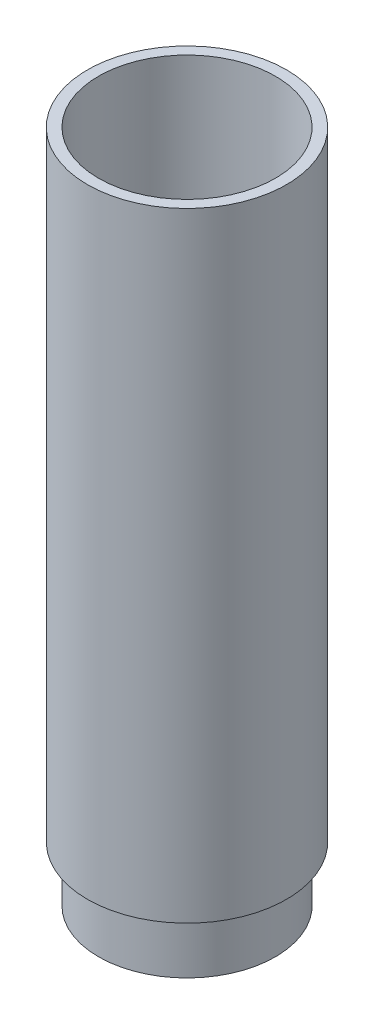
SolidWorks part; units mm, degrees
ref_plane "Front Plane" through (0, 0, 0) normal (0, 0, 1) x (1, 0, 0)
ref_plane "Top Plane" through (0, 0, 0) normal (0, 1, 0) x (1, 0, 0)
ref_plane "Right Plane" through (0, 0, 0) normal (1, 0, 0) x (0, 0, -1)
sketch "Sketch1" plane through (0, 0, 0) normal (0, 1, 0) x (1, 0, 0)
  circle A0 centre (0, 0) radius 8
  circle A1 centre (0, 0) radius 7
extrude "Boss-Extrude1" add sketch "Sketch1" along normal blind 15
ref_plane "Plane1" through (0, 10, 0) normal (0, 1, 0) x (1, 0, 0)
sketch "Sketch2" plane through (0, 10, 0) normal (0, 1, 0) x (1, 0, 0)
  circle A0 centre (0, 0) radius 8
  circle A1 centre (0, 0) radius 9
extrude "Boss-Extrude2" add sketch "Sketch2" along normal blind 120
sketch "Sketch3" plane through (0, 0, 0) normal (0, 1, 0) x (1, 0, 0)
  circle A0 centre (0, 0) radius 8
  circle A1 centre (0, 0) radius 7
extrude "Cut-Extrude1" cut sketch "Sketch3" along normal blind 5
sketch "Sketch4" plane through (0, 0, 0) normal (0, 0, 1) x (1, 0, 0)
  line L0 (-9, 130) -> (-9, 10) construction
  line L1 (9, 130) -> (-9, 130)
  line L2 (9, 130) -> (9, 89.0594)
  line L3 (9, 89.0594) -> (-9, 89.0594)
  line L4 (-9, 130) -> (-9, 89.0594)
extrude "Cut-Extrude2" cut sketch "Sketch4" against normal blind 31 and the other way blind 31
sketch "Sketch5" plane through (0, 0, 0) normal (0, 0, 1) x (1, 0, 0)
  line L0 (9, 89.0594) -> (-9, 89.0594) construction
  line L1 (9, 89.0594) -> (-9, 89.0594)
  line L2 (9, 89.0594) -> (9, 65.9801)
  line L3 (9, 65.9801) -> (-9, 65.9801)
  line L4 (-9, 89.0594) -> (-9, 65.9801)
  line L5 (-9, 89.0594) -> (-9, 10) construction
extrude "Cut-Extrude3" cut sketch "Sketch5" against normal blind 31 and the other way blind 31
